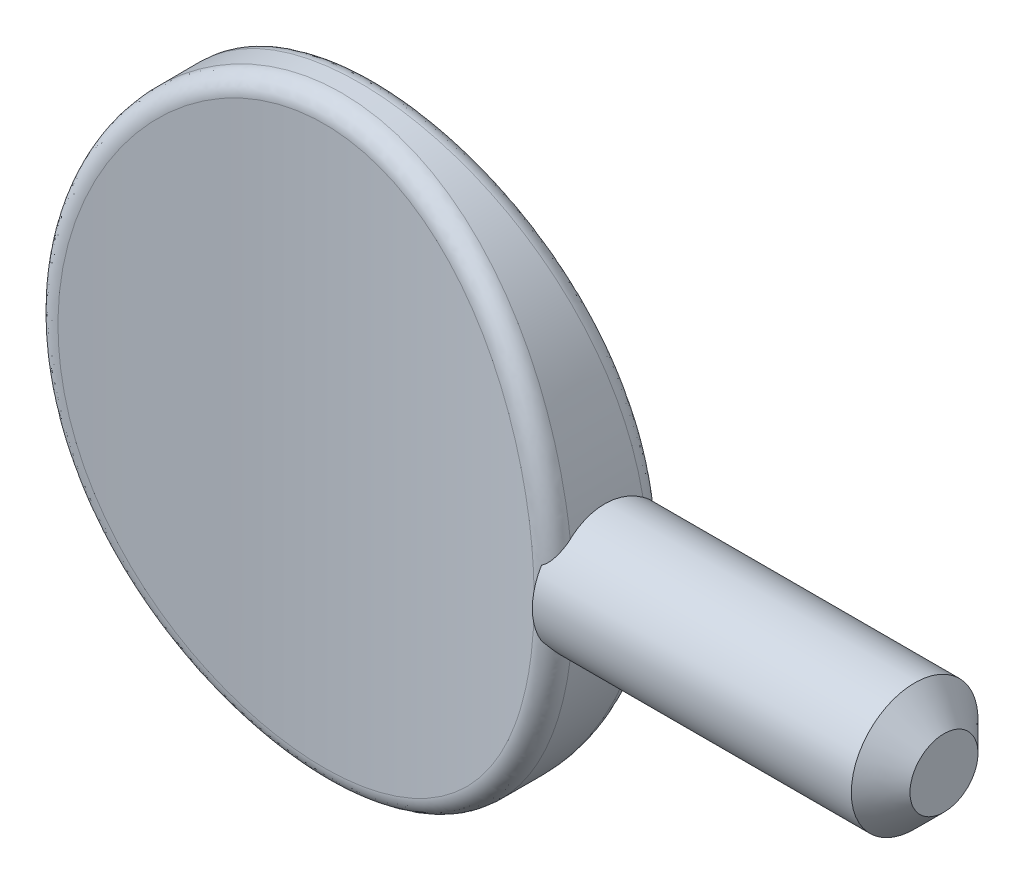
SolidWorks part; units mm, degrees
ref_plane "Front" through (0, 0, 0) normal (0, 0, 1) x (1, 0, 0)
ref_plane "Top" through (0, 0, 0) normal (0, 1, 0) x (1, 0, 0)
ref_plane "Right" through (0, 0, 0) normal (1, 0, 0) x (0, 0, -1)
ref_axis "Axis1" through (-50, 0, 0) along (1, 0, 0)
sketch "Sketch1" plane through (0, 0, 0) normal (0, 0, 1) x (1, 0, 0)
  line L0 (0, 0) -> (22.606, 0) construction
  line L1 (13.208, -2.413) -> (13.208, 2.413)
  line L2 (13.208, -2.413) -> (9.6776, -2.413) construction
  ellipse E0 centre (0, 0) end of major axis (0, -11.303) minor radius 9.906
  dimension "D2" = 3.302
  dimension "B" = 19.812
  dimension "L" = 12.7
extrude "Extrude1" add sketch "Sketch1" along normal mid plane 4.572
sketch "Sketch2" plane through (0, 0, 0) normal (0, 1, 0) x (1, 0, 0)
  line L0 (9.906, 2.286) -> (-9.906, 2.286) construction
  line L1 (0, 0) -> (0, 1.1721) construction
  line L2 (-1.7991, 0) -> (2.0444, 0) construction
  line L3 (-9.906, -2.286) -> (9.906, -2.286) construction
  line L6 (-9.906, 2.286) -> (-9.906, -2.286)
  line L7 (9.906, 2.286) -> (9.906, -2.286)
  arc A0 (-9.906, 2.286) -> (9.906, 2.286) centre (0, 40.2844) ccw
  arc A1 (-9.906, -2.286) -> (9.906, -2.286) centre (0, -40.2844) cw
extrude "Cut-Extrude1" cut sketch "Sketch2" against normal through all and the other way through all flip side to cut
fillet "Fillet3" radius 0.6773 2 edges at (-9.9037, -0.2444, 2.2854) (2.9825, 10.7785, -1.1294)
sketch "Sketch3" plane through (0, 0, 0) normal (0, 1, 0) x (1, 0, 0)
  line L0 (22.606, 0) -> (22.606, 1.2954)
  line L1 (0, 0) -> (21.0288, 0) construction
  line L2 (0, 0) -> (22.606, 0) construction
  line L3 (13.208, 2.413) -> (13.208, 0) construction
  line L4 (13.208, 2.413) -> (21.4884, 2.413)
  line L5 (22.606, 1.2954) -> (21.4884, 2.413)
  line L6 (13.208, 2.413) -> (9.3367, 2.413)
  line L7 (9.0722, 2.0783) -> (9.0722, 0)
  line L8 (9.3367, 0) -> (9.3367, 2.413) construction
  line L9 (9.0722, 0) -> (22.606, 0)
  arc A0 (9.3367, 2.413) -> (9.0722, 2.0783) centre (8.9927, 2.413) cw
  arc A3 (-9.906, 2.286) -> (9.906, 2.286) centre (0, 40.2844) ccw construction
  dimension "D1" = 45
revolve "Revolve1" add sketch "Sketch3" angle 360 about L0
cosmetic thread "Cosmetic Thread1" [suppressed]
sketch "Sketch4" plane through (0, 0, 0) normal (0, 0, 1) x (1, 0, 0)
  line L0 (0, 0) -> (27.7993, 0) construction
  line L1 (21.3051, 2.413) -> (21.4884, 2.0955)
  line L2 (21.4884, 2.0955) -> (21.6717, 2.413)
  line L3 (21.6717, 2.413) -> (21.6717, 2.7796)
  line L4 (21.6717, 2.7796) -> (21.3051, 2.7796)
  line L5 (21.3051, 2.7796) -> (21.3051, 2.413)
  line L6 (21.4884, 2.413) -> (21.4884, -2.413) construction
  dimension "D1" = 4.191
  dimension "D2" = 4.826
revolve "Cut-Revolve10" [suppressed] cut sketch "Sketch4" angle 360 about L0
pattern_linear "LPattern10" [suppressed] count 23 along (-1, 0, 0) of bodies 109
equation "\"D2@Sketch1\" = \"B@Sketch1\" / 6"
equation "\"D1@Fillet3\" = \"C1@Sketch2\" / 3"
equation "\"DIA@Sketch3\" = \"D@Sketch1\""
equation "\"D1@Cosmetic Thread1\" = \"L@Sketch1\" -  ( \"D@Sketch1\" - \"flat_dia@Sketch3\" )  / 2"
equation "\"D1@Sketch4\" = \"D2@Cosmetic Thread1\""
equation "\"D2@Sketch4\" = \"DIA@Sketch3\""
equation "\"D1@LPattern10\" = \"D1@Cosmetic Thread1\" / \"P@LPattern10\" "
